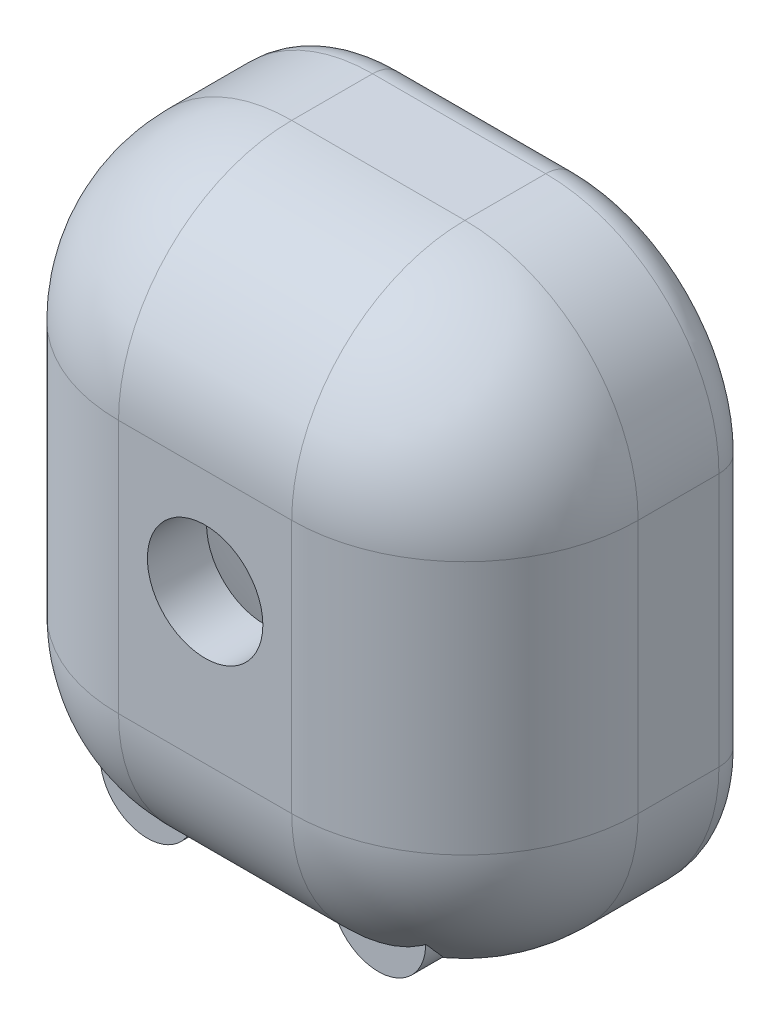
SolidWorks part; units mm, degrees
material "Polyetheretherketone (PEEK)"
ref_plane "Front Plane" through (0, 0, 0) normal (0, 0, 1) x (1, 0, 0)
ref_plane "Top Plane" through (0, 0, 0) normal (0, 1, 0) x (1, 0, 0)
ref_plane "Right Plane" through (0, 0, 0) normal (1, 0, 0) x (0, 0, -1)
sketch "Sketch1" plane through (0, 0, 0) normal (0, 0, 1) x (1, 0, 0)
  line L0 (-22.5, 0) -> (22.5, 0)
  line L1 (22.5, 0) -> (22.5, 52)
  line L2 (22.5, 52) -> (-22.5, 52)
  line L3 (-22.5, 52) -> (-22.5, 0)
  point P0 (0, 0)
  dimension "D1" = 52
  dimension "D2" = 45
extrude "Boss-Extrude1" add sketch "Sketch1" along normal mid plane 25
sketch "Sketch2" plane through (0, 0, -12.5) normal (0, 0, -1) x (-1, 0, 0)
  line L0 (0, 0) -> (0, 52) construction
  line L1 (-22.5, 52) -> (22.5, 52) construction
  line L2 (22.5, 0) -> (-22.5, 0) construction
  circle A0 centre (-10, 6) radius 4.1
  circle A1 centre (10, 6) radius 4.1
  dimension "D1" = 8.2
  dimension "D2" = 10
  dimension "D3" = 6
extrude "Cut-Extrude1" cut sketch "Sketch2" against normal blind 20
sketch "Sketch4" plane through (0, 0, -12.5) normal (0, 0, -1) x (-1, 0, 0)
  line L0 (-20.5, 27.9034) -> (20.5, 27.9034) construction
  line L1 (-20.5, 27.9034) -> (20.5, 27.9034)
  arc A0 (-20.5, 27.9034) -> (20.5, 27.9034) centre (0, 27.9034) ccw
  dimension "D1" = 41
revolve "Cut-Revolve2" cut sketch "Sketch4" angle 360 about L0
sketch "Sketch5" plane through (0, 0, 12.5) normal (0, 0, 1) x (1, 0, 0)
  circle A0 centre (0, 27.9034) radius 5
  arc A1 (10.1578, 10.097) -> (-10.1578, 10.097) centre (0, 27.9034) ccw construction
  dimension "D1" = 10
extrude "Cut-Extrude2" cut sketch "Sketch5" against normal through all
fillet "Fillet1" radius 15 8 edges at (-22.5, 0, 0) (-22.5, 52, 0) (0, 52, 12.5) (-22.5, 26, 12.5) (0, 0, 12.5) (22.5, 0, 0) (22.5, 26, 12.5) (22.5, 52, 0)
fillet "Fillet2" radius 3 8 edges at (18.1066, 47.6066, -12.5) (22.5, 26, -12.5) (18.1066, 4.3934, -12.5) (0, 0, -12.5) (-18.1066, 4.3934, -12.5) (-22.5, 26, -12.5) (-18.1066, 47.6066, -12.5) (0, 52, -12.5)
